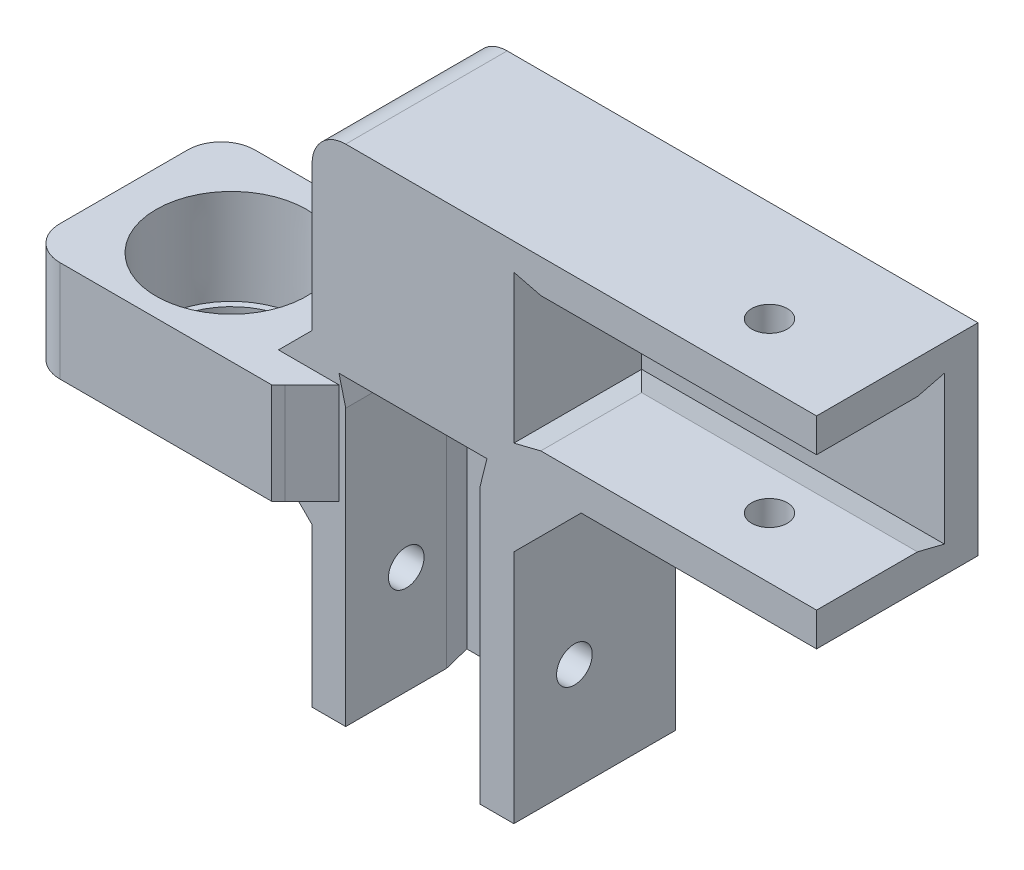
SolidWorks part; units mm, degrees
ref_plane "Front Plane" through (0, 0, 0) normal (0, 0, 1) x (1, 0, 0)
ref_plane "Top Plane" through (0, 0, 0) normal (0, 1, 0) x (1, 0, 0)
ref_plane "Right Plane" through (0, 0, 0) normal (1, 0, 0) x (0, 0, -1)
sketch "Sketch1" plane through (0, 0, 0) normal (0, 0, 1) x (1, 0, 0)
  line L1 (0, 0) -> (75, 0)
  line L2 (0, 0) -> (0, 75)
  line L3 (0, 75) -> (75, 75)
  line L4 (75, 0) -> (75, 75)
  dimension "D1" = 75
  dimension "D2" = 75
extrude "Boss-Extrude1" add sketch "Sketch1" along normal blind 24
sketch "Sketch2" plane through (0, 0, 0) normal (0, -1, 0) x (1, 0, 0)
  line L1 (25, 24) -> (5, 24)
  line L2 (25, 24) -> (25, 5)
  line L3 (25, 5) -> (5, 5)
  line L4 (5, 24) -> (5, 5)
  line L6 (0, 0) -> (75, 0) construction
  line L7 (0, 24) -> (75, 24) construction
  line L8 (0, 24) -> (0, 0) construction
  dimension "D1" = 5
  dimension "D2" = 5
  dimension "D3" = 20
extrude "Cut-Extrude1" cut sketch "Sketch2" against normal blind 45
sketch "Sketch3" plane through (75, 0, 0) normal (1, 0, 0) x (0, 0, -1)
  line L1 (-24, 50) -> (-5, 50)
  line L2 (-24, 50) -> (-24, 70)
  line L3 (-24, 70) -> (-5, 70)
  line L4 (-5, 50) -> (-5, 70)
  line L5 (-24, 75) -> (0, 75) construction
  line L6 (-24, 0) -> (-24, 75) construction
  line L9 (0, 0) -> (0, 75) construction
  dimension "D1" = 5
  dimension "D2" = 20
  dimension "D3" = 5
extrude "Cut-Extrude2" cut sketch "Sketch3" against normal blind 45
sketch "Sketch4" plane through (0, 0, 24) normal (0, 0, 1) x (1, 0, 0)
  line L0 (30, 50) -> (75, 50) construction
  line L1 (75, 0) -> (30, 0)
  line L2 (75, 0) -> (75, 45)
  line L3 (75, 45) -> (30, 45)
  line L4 (30, 0) -> (30, 45)
  line L5 (25, 45) -> (25, 0) construction
  dimension "D1" = 5
  dimension "D2" = 5
extrude "Cut-Extrude3" cut sketch "Sketch4" against normal through all both and the other way through all
fillet "Fillet1" radius 5 1 edges at (0, 75, 12)
chamfer "Chamfer1" distance 10 angle 45 1 edges at (30, 45, 12)
sketch "Sketch5" plane through (0, 0, 0) normal (-1, 0, 0) x (0, 0, 1)
  line L1 (29, 43.5) -> (0, 43.5)
  line L2 (29, 43.5) -> (29, 28.5)
  line L3 (29, 28.5) -> (0, 28.5)
  line L4 (0, 43.5) -> (0, 28.5)
  line L6 (0, 70) -> (0, 0) construction
  dimension "D1" = 28.5
  dimension "D2" = 29
  dimension "D3" = 15
extrude "Boss-Extrude2" add sketch "Sketch5" along normal blind 37.5
sketch "Sketch6" plane through (0, 43.5, 0) normal (0, 1, 0) x (1, 0, 0)
  circle A0 centre (-21, -15) radius 11.2
  dimension "D1" = 22.4
extrude "Cut-Extrude4" cut sketch "Sketch6" against normal offset from surface (14 mm away) 1 up to face at (-15, 28.5, 16.4)
fillet "Fillet2" radius 5 2 edges at (-37.5, 36, 29) (-37.5, 36, 0)
chamfer "Chamfer3" distance 5 angle 45 2 edges at (0, 43.5, 12) (0, 28.5, 12)
sketch "Sketch7" plane through (0, 45, 0) normal (0, -1, 0) x (1, 0, 0)
  line L0 (75, 0) -> (75, 24) construction
  line L1 (40, 24) -> (75, 24) construction
  circle A0 centre (59, 15) radius 2.65
  dimension "D1" = 5.3
  dimension "D2" = 16
  dimension "D3" = 9
extrude "Cut-Extrude5" cut sketch "Sketch7" against normal through all both and the other way through all
sketch "Sketch8" plane through (30, 0, 0) normal (1, 0, 0) x (0, 0, -1)
  line L0 (0, 0) -> (-24, 0) construction
  line L1 (-24, 0) -> (-24, 35) construction
  circle A0 centre (-15, 16) radius 2.65
  dimension "D1" = 5.3
  dimension "D2" = 16
  dimension "D3" = 9
extrude "Cut-Extrude6" cut sketch "Sketch8" against normal through all both and the other way through all
sketch "Sketch9" plane through (0, 0, 5) normal (0, 0, 1) x (1, 0, 0)
  line L0 (5, 0) -> (25, 0) construction
  line L1 (25, 45) -> (25, 0) construction
  circle A0 centre (15, 22.5) radius 2.65
  dimension "D1" = 5.3
  dimension "D2" = 22.5
  dimension "D3" = 10
extrude "Cut-Extrude7" cut sketch "Sketch9" against normal blind 10
sketch "Sketch10" plane through (0, 0, 5) normal (0, 0, 1) x (1, 0, 0)
  line L0 (30, 70) -> (75, 70) construction
  line L1 (75, 50) -> (75, 70) construction
  circle A0 centre (52.5, 60) radius 2.65
  dimension "D1" = 5.3
  dimension "D2" = 10
  dimension "D3" = 22.5
extrude "Cut-Extrude8" cut sketch "Sketch10" against normal blind 10
sketch "Sketch11" plane through (0, 0, 24) normal (0, 0, 1) x (1, 0, 0)
  line L0 (34, 70) -> (30, 71)
  line L1 (30, 70) -> (75, 70) construction
  line L2 (30, 71) -> (30, 70)
  line L3 (30, 70) -> (34, 70)
  line L4 (30, 50) -> (34, 50)
  line L5 (30, 50) -> (75, 50) construction
  line L6 (34, 50) -> (30, 49)
  line L7 (30, 49) -> (30, 50)
  line L10 (26, 45) -> (25, 41)
  line L14 (25, 45) -> (25, 0) construction
  line L16 (5, 45) -> (4, 45)
  line L18 (4, 45) -> (5, 41)
  line L19 (25, 45) -> (5, 45) construction
  line L20 (5, 41) -> (5, 45)
  line L21 (25, 45) -> (26, 45)
  line L22 (25, 41) -> (25, 45)
  dimension "D1" = 4
  dimension "D2" = 1
  dimension "D3" = 1
  dimension "D4" = 4
  dimension "D5" = 1
  dimension "D6" = 1
  dimension "D7" = 4
  dimension "D8" = 4
extrude "Cut-Extrude12" cut sketch "Sketch11" against normal up to surface (19 mm away) up to face at (17.65, 22.5, 5)
sketch "Sketch12" plane through (0, 0, 0) normal (0, -1, 0) x (1, 0, 0)
  line L0 (5, 5) -> (4, 5)
  line L1 (4, 5) -> (5, 9)
  line L2 (5, 24) -> (5, 5) construction
  line L3 (5, 9) -> (5, 5)
  line L4 (25, 5) -> (26, 5)
  line L5 (26, 5) -> (25, 9)
  line L6 (25, 5) -> (25, 24) construction
  line L7 (25, 9) -> (25, 5)
  dimension "D1" = 4
  dimension "D2" = 4
  dimension "D3" = 1
  dimension "D4" = 1
extrude "Cut-Extrude13" cut sketch "Sketch12" against normal up to surface (45 mm away) up to face at (15, 45, 14.5)
sketch "Sketch13" plane through (75, 0, 0) normal (1, 0, 0) x (0, 0, -1)
  line L0 (-5, 50) -> (-5, 49)
  line L1 (-5, 49) -> (-9, 50)
  line L2 (-24, 50) -> (-5, 50) construction
  line L3 (-9, 50) -> (-5, 50)
  line L4 (-5, 70) -> (-5, 71)
  line L5 (-5, 71) -> (-9, 70)
  line L6 (-5, 70) -> (-24, 70) construction
  line L7 (-9, 70) -> (-5, 70)
  dimension "D1" = 1
  dimension "D2" = 4
  dimension "D3" = 4
  dimension "D4" = 1
extrude "Cut-Extrude14" cut sketch "Sketch13" against normal up to surface (45 mm away) up to face at (30, 60, 14.5)
sketch "Sketch14" plane through (0, 29.5, 0) normal (0, 1, 0) x (1, 0, 0)
  circle A0 centre (-21, -15) radius 10
  dimension "D1" = 20
extrude "Cut-Extrude15" cut sketch "Sketch14" against normal blind 10
chamfer "Chamfer5" distance 4 angle 45 1 edges at (0, 36, 24)
chamfer "Chamfer6" distance 1 angle 45 1 edges at (0, 36, 29)
chamfer "Chamfer8" distance 15 angle 0.9 1 edges at (-32.2, 29.5, 15) first distance on face at (-32.2, 29.5, 15)
mirror "Mirror1" [suppressed] of bodies 117 108
delete or keep bodies "Body-Delete/Keep 1" [suppressed] type delete bodies bodies 117
